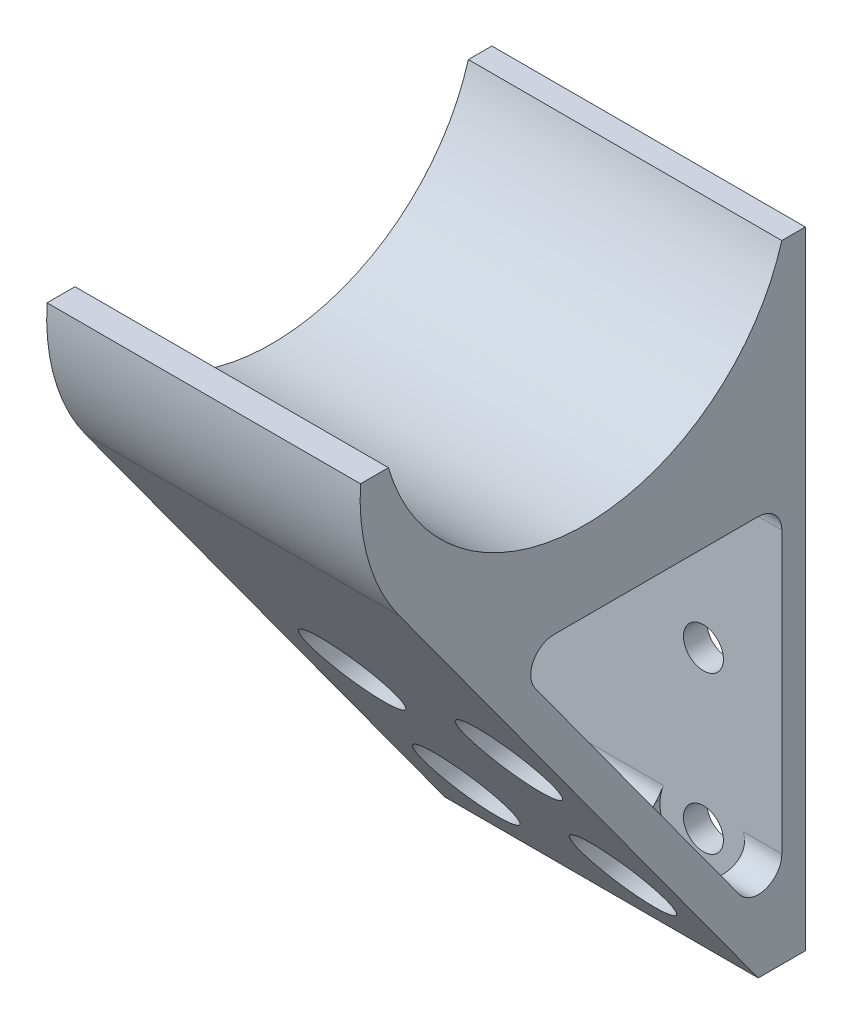
SolidWorks part; units mm, degrees
ref_plane "Спереди" through (0, 0, 0) normal (0, 0, 1) x (1, 0, 0)
ref_plane "Сверху" through (0, 0, 0) normal (0, 1, 0) x (1, 0, 0)
ref_plane "Справа" through (0, 0, 0) normal (1, 0, 0) x (0, 0, -1)
sketch "Эскиз1" plane through (0, 0, 0) normal (1, 0, 0) x (0, 0, -1)
  line L0 (0, 0) -> (0, -80)
  line L1 (0, 0) -> (-3, 0)
  line L2 (-3, 0) -> (-77.8373, 0) construction
  line L3 (-53.2, 0) -> (-56.7604, 0)
  line L4 (0, -80) -> (-6, -80)
  line L5 (-6, -80) -> (-51.794, -17.0803)
  line L7 (-3, -32) -> (-3, -67.78)
  line L10 (-8.4256, -69.5454) -> (-34.4668, -33.7654)
  line L11 (-32.0413, -29) -> (-6, -29)
  line L12 (-77.8373, 7.25) -> (30.3216, 7.25) construction
  line L13 (-28.1, 11.9619) -> (-28.1, -20.7143) construction
  arc A1 (-56.7604, 0) -> (-51.794, -17.0803) centre (-30.6015, -1.656) ccw
  arc A2 (-3, -67.78) -> (-8.4256, -69.5454) centre (-6, -67.78) cw
  arc A3 (-6, -29) -> (-3, -32) centre (-6, -32) cw
  arc A4 (-34.4668, -33.7654) -> (-32.0413, -29) centre (-32.0413, -32) cw
  arc A5 (-53.2, 0) -> (-3, 0) centre (-28.1, 7.25) ccw
  point P16 (-3, -77)
  dimension "D3" = 6
  dimension "D7" = 3
  dimension "D8" = 7.25
  dimension "D1" = 80
  dimension "D2" = 3
  dimension "D5" = 3
  dimension "D6" = 3
extrude "Бобышка-Вытянуть1" add sketch "Эскиз1" along normal blind 40
sketch "Эскиз2" plane through (0, 0, 0) normal (0, 0, -1) x (-1, 0, 0)
  line L0 (-44.7022, -70) -> (3.7377, -70) construction
  line L1 (-40, -80) -> (0, -80) construction
  line L2 (-45.5596, -50) -> (11.4538, -50) construction
  line L3 (-40, -80) -> (-40, 0) construction
  circle A0 centre (-30, -50) radius 2.55
  circle A1 centre (-10, -50) radius 2.55
  circle A2 centre (-10, -70) radius 2.55
  circle A3 centre (-30, -70) radius 2.55
  dimension "D3" = 5.1
  dimension "D4" = 5.1
  dimension "D5" = 5.1
  dimension "D6" = 5.1
  dimension "D8" = 5.1
  dimension "D9" = 10
  dimension "D10" = 20
  dimension "D11" = 20
  dimension "D1" = 10
  dimension "D2" = 20
  dimension "D7" = 10
extrude "Вырез-Вытянуть1" cut sketch "Эскиз2" against normal through all
ref_plane "Плоскость1" through (0, 0, 3) normal (0, 0, 1) x (1, 0, 0)
sketch "Эскиз3" plane through (0, 0, 3) normal (0, 0, 1) x (1, 0, 0)
  circle A0 centre (30, -50) radius 2.55 construction
  circle A1 centre (30, -50) radius 2.55
  circle A2 centre (10, -50) radius 2.55 construction
  circle A3 centre (10, -50) radius 2.55
  circle A4 centre (10, -70) radius 2.55 construction
  circle A5 centre (10, -70) radius 2.55
  circle A6 centre (30, -70) radius 2.55 construction
  circle A7 centre (30, -70) radius 2.55
  circle A8 centre (10, -50) radius 5.55
  circle A9 centre (30, -50) radius 5.55
  circle A10 centre (10, -70) radius 5.55
  circle A11 centre (30, -70) radius 5.55
  dimension "D1" = 3
  dimension "D2" = 3
  dimension "D3" = 3
  dimension "D4" = 3
extrude "Вырез-Вытянуть2" cut sketch "Эскиз3" along normal up to surface (24.8345 mm away) up to face at (30, -72.55, 11.4222)
